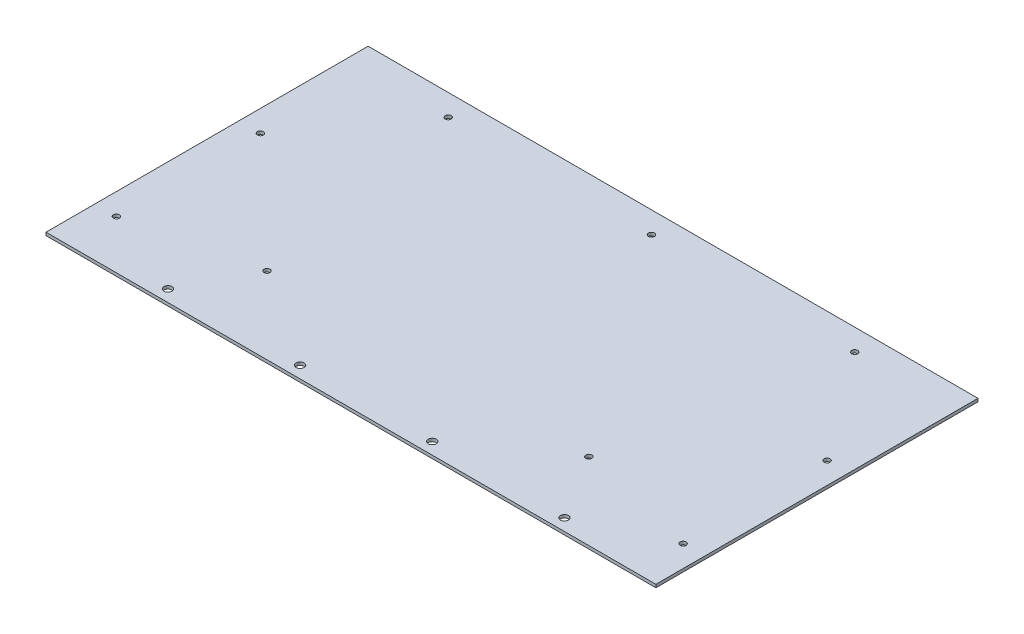
SolidWorks part; units mm, degrees
material "6061-T6 (SS)"
ref_plane "X-Y Datum" through (0, 0, 0) normal (0, 0, 1) x (1, 0, 0)
ref_plane "X-Z Datum" through (0, 0, 0) normal (0, 1, 0) x (1, 0, 0)
ref_plane "Y-Z Datum" through (0, 0, 0) normal (1, 0, 0) x (0, 0, -1)
sketch "Sketch1" plane through (0, 0, 0) normal (0, 0, 1) x (1, 0, 0)
  line L1 (-228.6, -1.143) -> (228.6, -1.143)
  line L2 (-228.6, -1.143) -> (-228.6, 1.143)
  line L3 (-228.6, 1.143) -> (228.6, 1.143)
  line L4 (228.6, -1.143) -> (228.6, 1.143)
  line L5 (-228.6, -1.143) -> (228.6, 1.143) construction
  line L6 (-228.6, 1.143) -> (228.6, -1.143) construction
  point P0 (0, 0)
  dimension "D1" = 2.286
  dimension "D2" = 457.2
extrude "Boss-Extrude1" add sketch "Sketch1" along normal blind 238.3152
sketch "Sketch2" plane through (0, 0, 0) normal (0, 0, -1) x (-1, 0, 0)
  line L22 (-228.6, 1.143) -> (-228.6, -1.143)
  line L23 (-228.6, -1.143) -> (228.6, -1.143)
  line L24 (228.6, -1.143) -> (228.6, 1.143)
  line L25 (228.6, 1.143) -> (-228.6, 1.143)
  line L26 (-228.6, 1.143) -> (-228.6, -1.143)
  line L27 (-228.6, -1.143) -> (228.6, -1.143)
  line L28 (228.6, -1.143) -> (228.6, 1.143)
  line L29 (228.6, 1.143) -> (-228.6, 1.143)
  line M6 (-228.6, -1.143) -> (228.6, -1.143)
  line M8 (228.6, 1.143) -> (-228.6, 1.143)
  dimension "D1" = 0
extrude "Boss-Extrude2" add sketch "Sketch2" along normal blind 3.175 contours M8 M6 | M8 M6 region at (0, 0, 0)
sketch "Sketch9" plane through (0, 1.143, 0) normal (0, 1, 0) x (1, 0, 0)
  line L0 (-146.05, -238.3152) -> (-146.05, -229.4252) construction
  line L1 (228.6, -238.3152) -> (-228.6, -238.3152) construction
  line L2 (-228.6, -238.3152) -> (-228.6, 3.175) construction
  circle A0 centre (-146.05, -229.4252) radius 3
  dimension "D2" = 82.55
  dimension "D3" = 6
  dimension "D1" = 8.89
extrude "Cut-Extrude10" cut sketch "Sketch9" against normal blind 2.54
pattern_linear "LPattern1" count 4 spacing 99.06 along (1, 0, 0) of "Cut-Extrude10"
sketch "Sketch10" plane through (0, -1.143, 0) normal (0, -1, 0) x (1, 0, 0)
  circle A0 centre (151.13, 229.4252) radius 3 construction
  circle A1 centre (52.07, 229.4252) radius 3 construction
  circle A2 centre (-46.99, 229.4252) radius 3 construction
  circle A3 centre (-146.05, 229.4252) radius 3 construction
  circle A4 centre (151.13, 229.4252) radius 3
  circle A5 centre (52.07, 229.4252) radius 3
  circle A6 centre (-46.99, 229.4252) radius 3
  circle A7 centre (-146.05, 229.4252) radius 3
sketch "Sketch12" plane through (0, -1.143, 0) normal (0, -1, 0) x (1, 0, 0)
  point P0 (-212.419, 93.7748)
  point P1 (-152.4, 13.0175)
  point P3 (0, 13.0175)
  point P5 (152.4, 13.0175)
  point P7 (212.419, 93.7748)
  point P9 (212.419, 201.7248)
  point P11 (120.65, 180.586)
  point P15 (-120.65, 180.586)
  point P17 (-212.419, 201.7248)
hole_wizard "M4 Clearance Hole1" positions "Sketch12" profile "Sketch13" hole size "M4" standard "ANSI Metric" end condition through all
sketch "Sketch13" plane through (-212.419, -1.143, 93.7748) normal (1, 0, 0) x (0, 0, -1)
  line L0 (0, 0) -> (0, 2.286)
  line L1 (0, 2.286) -> (2.25, 2.286)
  line L2 (2.25, 2.286) -> (2.25, 0)
  line L5 (2.25, 0) -> (0, 0)
  line L11 (0, -6.35) -> (0, 107.95) construction
  dimension "Thru Hole Dia." = 4.5
  dimension "Thru Hole Depth" = 2.286
